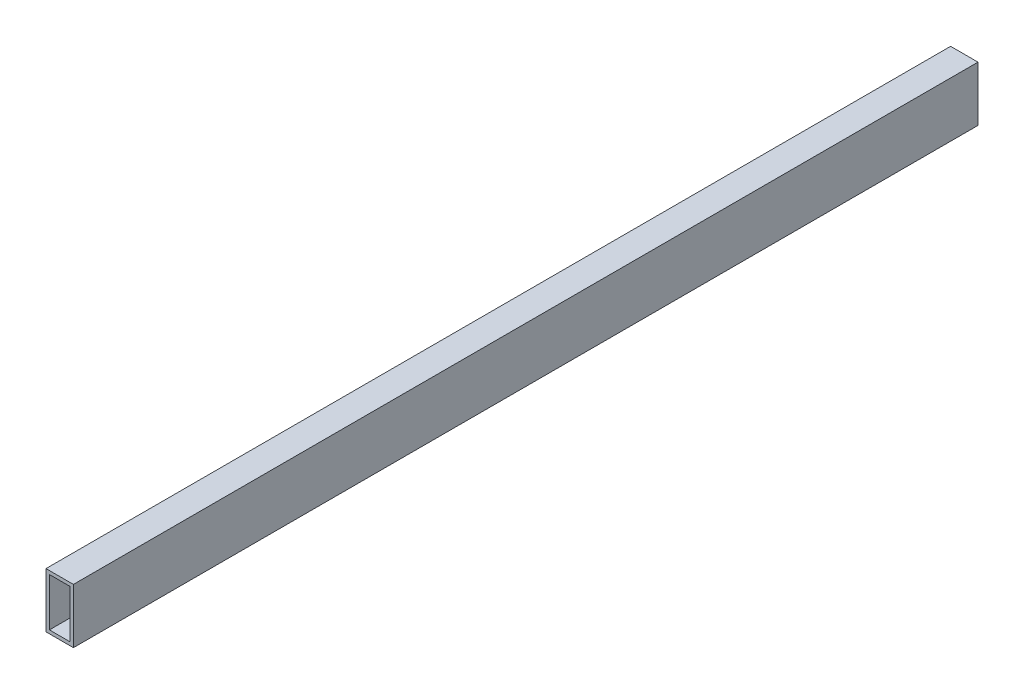
SolidWorks part; units mm, degrees
ref_plane "Front Plane" through (0, 0, 0) normal (0, 0, 1) x (1, 0, 0)
ref_plane "Top Plane" through (0, 0, 0) normal (0, 1, 0) x (1, 0, 0)
ref_plane "Right Plane" through (0, 0, 0) normal (1, 0, 0) x (0, 0, -1)
sketch "Sketch1" plane through (0, 0, 0) normal (0, 0, 1) x (1, 0, 0)
  line L1 (-12.7, -25.4) -> (12.7, -25.4)
  line L2 (-12.7, -25.4) -> (-12.7, 25.4)
  line L3 (-12.7, 25.4) -> (12.7, 25.4)
  line L4 (12.7, -25.4) -> (12.7, 25.4)
  line L5 (-12.7, -25.4) -> (12.7, 25.4) construction
  line L6 (-12.7, 25.4) -> (12.7, -25.4) construction
  line L7 (-9.525, -22.225) -> (9.525, -22.225)
  line L8 (-9.525, -22.225) -> (-9.525, 22.225)
  line L9 (-9.525, 22.225) -> (9.525, 22.225)
  line L10 (9.525, -22.225) -> (9.525, 22.225)
  line L11 (-9.525, -22.225) -> (9.525, 22.225) construction
  line L12 (-9.525, 22.225) -> (9.525, -22.225) construction
  point P0 (0, 0)
  point P1 (0, 0)
  point P7 (0, 0)
  dimension "D1" = 25.4
  dimension "D2" = 50.8
  dimension "D3" = 3.175
  dimension "D4" = 3.175
extrude "Boss-Extrude1" add sketch "Sketch1" along normal blind 838.2
